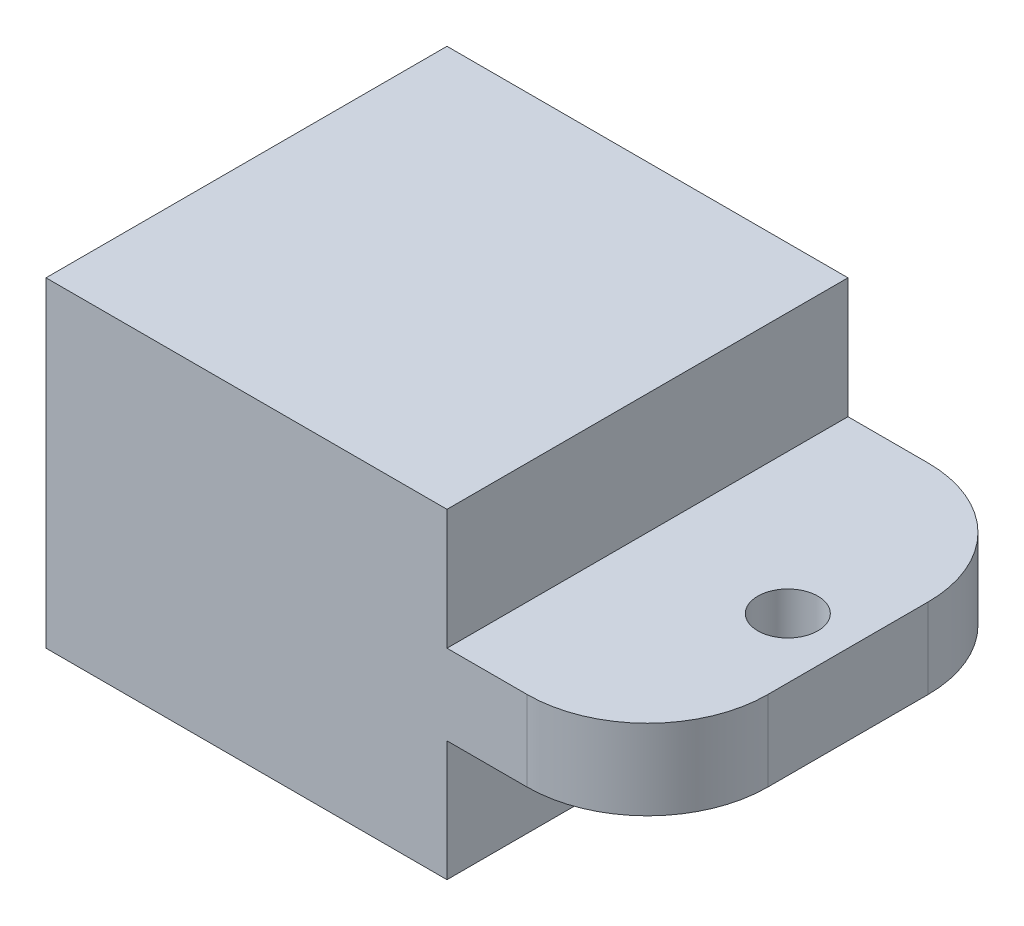
SolidWorks part; units mm, degrees
ref_plane "Front Plane" through (0, 0, 0) normal (0, 0, 1) x (1, 0, 0)
ref_plane "Top Plane" through (0, 0, 0) normal (0, 1, 0) x (1, 0, 0)
ref_plane "Right Plane" through (0, 0, 0) normal (1, 0, 0) x (0, 0, -1)
sketch "Sketch1" plane through (0, 0, 0) normal (0, 0, 1) x (1, 0, 0)
  line L0 (0, 0) -> (-75, 0)
  line L1 (-75, 0) -> (-75, 40)
  line L2 (-75, 40) -> (25, 40)
  line L3 (25, 40) -> (25, 10)
  line L4 (25, 10) -> (75, 10)
  line L5 (75, 10) -> (75, 0)
  line L6 (75, 0) -> (0, 0)
  point P5 (109.3966, 0)
  point P9 (0, 0)
  point P10 (0, 0)
  dimension "D1" = 75
  dimension "D2" = 75
  dimension "D3" = 100
  dimension "D4" = 40
  dimension "D5" = 10
  dimension "D6" = 50
extrude "Boss-Extrude1" add sketch "Sketch1" along normal blind 50 and the other way blind 50
mirror "Mirror1" about plane through (0, 0, -50) normal (0, -1, 0) of "Boss-Extrude1"
sketch "Sketch2" plane through (0, 10, 0) normal (0, 1, 0) x (1, 0, 0)
  line L0 (75, 50) -> (25, 50) construction
  circle A0 centre (60, 0) radius 7.5
  dimension "D1" = 50
  dimension "D2" = 15
extrude "Cut-Extrude1" cut sketch "Sketch2" against normal through all
fillet "Fillet1" radius 30 1 edges at (75, 0, -50)
fillet "Fillet2" radius 30 1 edges at (75, 0, 50)
